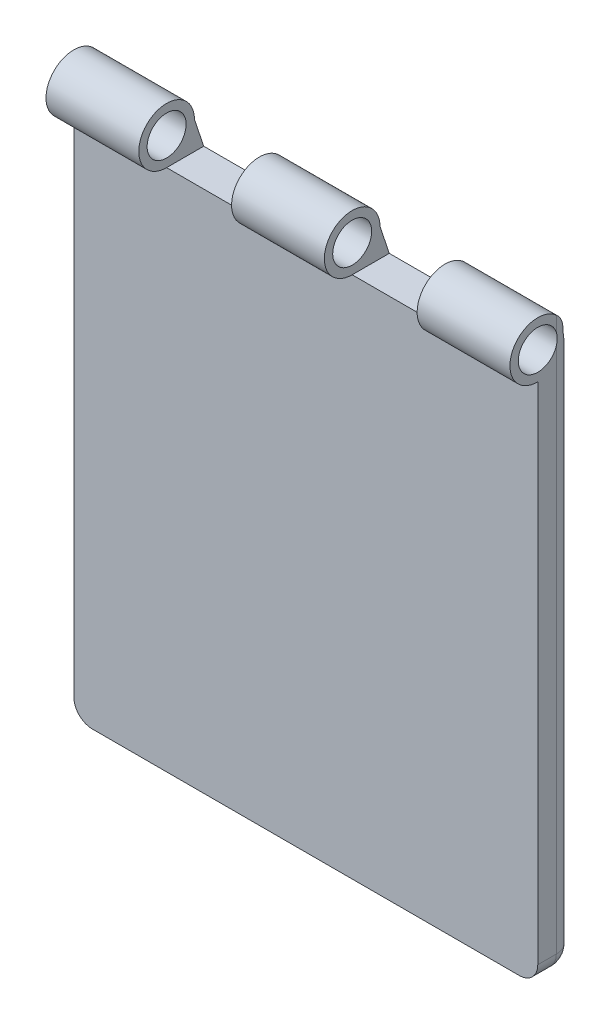
SolidWorks part; units mm, degrees
ref_plane "Front Plane" through (0, 0, 0) normal (0, 0, 1) x (1, 0, 0)
ref_plane "Top Plane" through (0, 0, 0) normal (0, 1, 0) x (1, 0, 0)
ref_plane "Right Plane" through (0, 0, 0) normal (1, 0, 0) x (0, 0, -1)
sketch "Sketch1" plane through (0, 0, 0) normal (0, 0, 1) x (1, 0, 0)
  line L1 (-12.5, -14.1) -> (12.5, -14.1)
  line L2 (-12.5, -14.1) -> (-12.5, 14.1)
  line L3 (-12.5, 14.1) -> (12.5, 14.1)
  line L4 (12.5, -14.1) -> (12.5, 14.1)
  line L5 (-12.5, -14.1) -> (12.5, 14.1) construction
  line L6 (-12.5, 14.1) -> (12.5, -14.1) construction
  point P0 (0, 0)
  dimension "D1" = 25
  dimension "D2" = 28.2
extrude "Boss-Extrude1" add sketch "Sketch1" along normal blind 2
sketch "Sketch5" plane through (-12.5, 0, 0) normal (-1, 0, 0) x (0, 0, 1)
  line L0 (2, 14.1) -> (2, 15.6) construction
  line L1 (0.5, 15.6) -> (0, 14.1)
  line L6 (0, 14.1) -> (0, -14.1)
  line L7 (0, -14.1) -> (2, -14.1)
  line L8 (2, -14.1) -> (2, 14.1)
  line L9 (2, 14.1) -> (0, 14.1)
  line L13 (2, 14.1) -> (0, 14.1)
  arc A0 (2, 14.1) -> (0.5, 15.6) centre (2, 15.6) ccw
  point P8 (0, 0)
  dimension "D1" = 3
  dimension "D2" = 0
extrude "Boss-Extrude2" add sketch "Sketch5" against normal blind 5
pattern_linear "LPattern1" count 3 spacing 10 along (1, 0, 0) of "Boss-Extrude2"
sketch "Sketch6" plane through (-12.5, 0, 0) normal (-1, 0, 0) x (0, 0, 1)
  circle A0 centre (2, 15.6) radius 1.5 construction
  circle A1 centre (2, 15.6) radius 1.05
extrude "Cut-Extrude1" cut sketch "Sketch6" against normal through all
fillet "Fillet1" radius 1 3 edges at (12.5, 0, 0) (0, -14.1, 0) (-12.5, 0, 0)
fillet "Fillet2" radius 1 4 edges at (12.2071, -13.8071, 0.2929) (-12.2071, -13.8071, 0.2929) (12.5, -14.1, 1.5) (-12.5, -14.1, 1.5)
